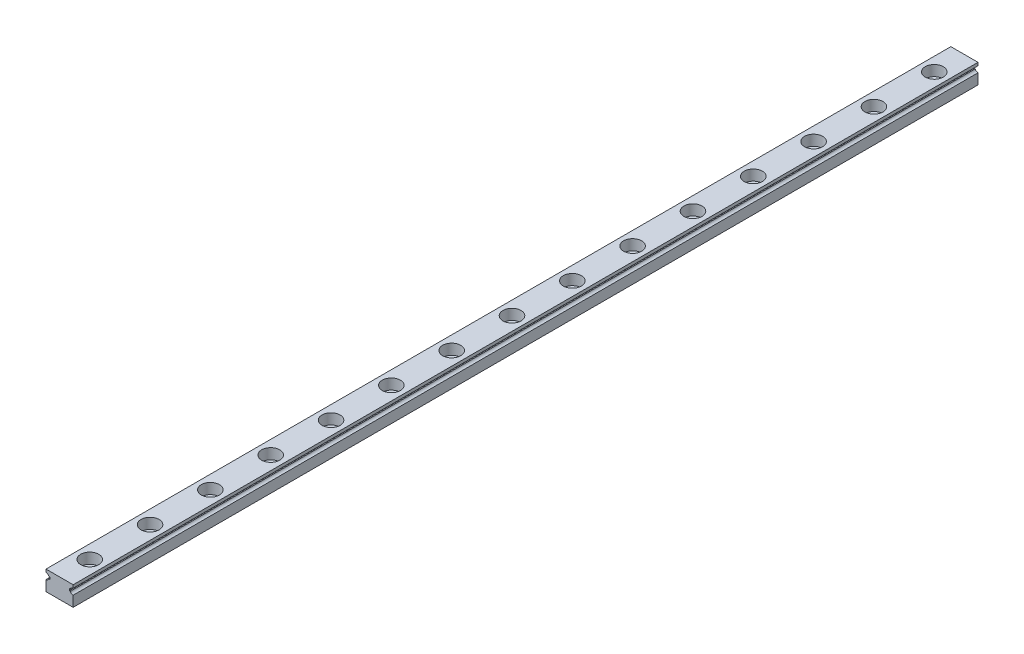
SolidWorks part; units mm, degrees
material "AISI 4340 Steel, annealed"
ref_plane "Спереди" through (0, 0, 0) normal (0, 0, 1) x (1, 0, 0)
ref_plane "Сверху" through (0, 0, 0) normal (0, 1, 0) x (1, 0, 0)
ref_plane "Справа" through (0, 0, 0) normal (1, 0, 0) x (0, 0, -1)
sketch "Sketch1" plane through (0, 0, 0) normal (0, 0, 1) x (1, 0, 0)
  line L0 (0, 0) -> (0, 5.7299) construction
  line L1 (-4.5, -3.25) -> (4.5, -3.25)
  line L2 (-4.5, -3.25) -> (-4.5, 0.25)
  line L3 (-4.5, 3.25) -> (4.5, 3.25)
  line L4 (4.5, -3.25) -> (4.5, 0.25)
  line L5 (-4.5, -3.25) -> (4.5, 3.25) construction
  line L6 (-4.5, 3.25) -> (4.5, -3.25) construction
  line L7 (-4.5, 2.25) -> (-4.5, 3.25)
  line L8 (-3.564, 0.898) -> (-3.2351, 0.898)
  line L9 (3.564, 0.898) -> (3.2351, 0.898)
  line L10 (-3.564, 1.602) -> (-3.2351, 1.602)
  line L11 (-3.2351, 0.898) -> (-3.2351, 1.602)
  line L12 (3.2351, 0.898) -> (3.2351, 1.602)
  line L13 (3.564, 1.602) -> (3.2351, 1.602)
  line L14 (4.5, 2.25) -> (4.5, 3.25)
  arc A0 (-3.564, 1.602) -> (-4.5, 2.25) centre (-4.5, 1.25) ccw
  arc A1 (-4.5, 0.25) -> (-3.564, 0.898) centre (-4.5, 1.25) ccw
  arc A2 (4.5, 0.25) -> (3.564, 0.898) centre (4.5, 1.25) cw
  arc A3 (3.564, 1.602) -> (4.5, 2.25) centre (4.5, 1.25) cw
  point P0 (0, 0)
  dimension "D3" = 1
  dimension "D1" = 9
  dimension "D2" = 6.5
  dimension "D4" = 2
extrude "Extrude1" add sketch "Sketch1" along normal blind 300
sketch "Sketch2" plane through (0, 3.25, 0) normal (0, 1, 0) x (1, 0, 0)
  line L0 (4.5, 0) -> (-4.5, 0) construction
  circle A0 centre (0, -10) radius 1.75
  circle A1 centre (0, -10) radius 3
  dimension "D1" = 3.5
  dimension "D2" = 6
  dimension "D3" = 10
extrude "Extrude2" cut sketch "Sketch2" against normal blind 3.5 contours A1
extrude "Extrude3" cut sketch "Sketch" against normal through all contours A0
sketch "Sketch" plane through (0, 3.25, 0) normal (0, 1, 0) x (1, 0, 0) same geometry as "Sketch2"
pattern_linear "LPattern1" count 16 spacing 20 along (0, 0, 1) of "Extrude2", "Extrude3"
